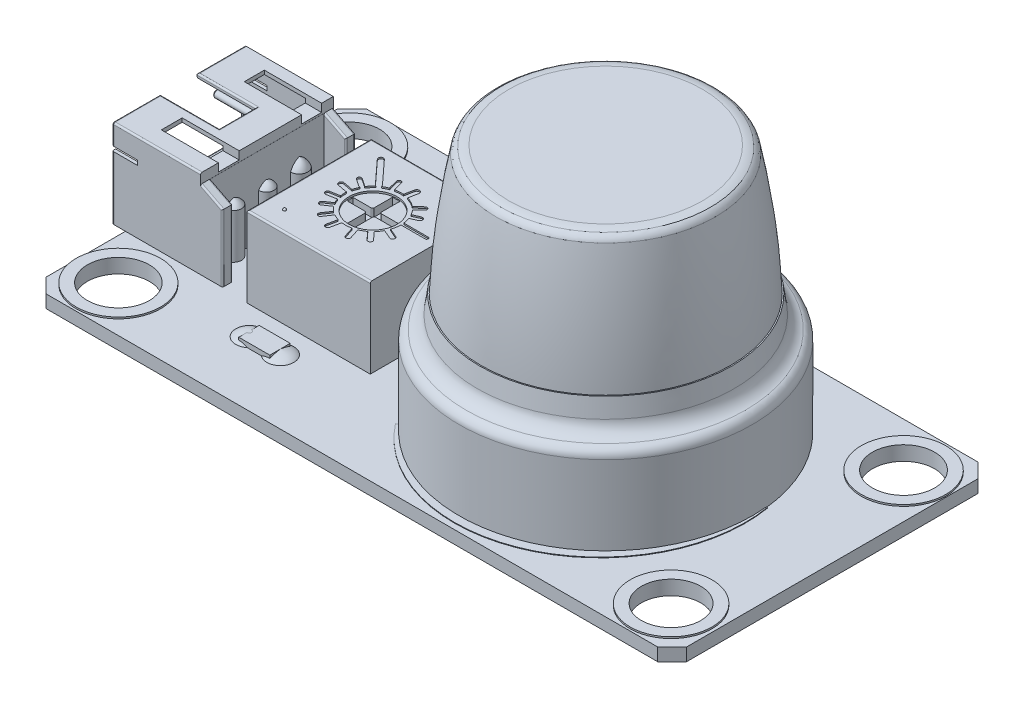
SolidWorks part; units mm, degrees
ref_plane "Alzado" through (0, 0, 0) normal (0, 0, 1) x (1, 0, 0)
ref_plane "Planta" through (0, 0, 0) normal (0, 1, 0) x (1, 0, 0)
ref_plane "Vista lateral" through (0, 0, 0) normal (1, 0, 0) x (0, 0, -1)
sketch "Croquis1" plane through (0, 0, 0) normal (0, 1, 0) x (1, 0, 0)
  line L1 (20, -10) -> (-20, -10)
  line L2 (20, -10) -> (20, 10)
  line L3 (20, 10) -> (-20, 10)
  line L4 (-20, -10) -> (-20, 10)
  line L5 (20, -10) -> (-20, 10) construction
  line L6 (20, 10) -> (-20, -10) construction
  point P0 (0, 0)
  dimension "D1" = 20
  dimension "D2" = 40
extrude "Saliente-Extruir1" add sketch "Croquis1" along normal blind 0.8
chamfer "Chaflán1" distance 0.9 angle 45 4 edges at (20, 0.4, 10) (20, 0.4, -10) (-20, 0.4, -10) (-20, 0.4, 10)
sketch "Croquis2" plane through (0, 0.8, 0) normal (0, 1, 0) x (1, 0, 0)
  circle A0 centre (-17.4865, 7.3544) radius 2.5635
  circle A1 centre (-17.4865, 7.3544) radius 1.8635
  dimension "D1" = 0.7
extrude "Saliente-Extruir2" add sketch "Croquis2" along normal blind 0.1
sketch "Croquis3" plane through (0, 0.8, 0) normal (0, 1, 0) x (1, 0, 0)
  circle A0 centre (-17.3437, -7.2372) radius 2.6343
  circle A2 centre (-17.3437, -7.2372) radius 1.9343
  dimension "D2" = 0.7
extrude "Saliente-Extruir3" add sketch "Croquis3" along normal blind 0.1
sketch "Croquis4" plane through (0, 0.8, 0) normal (0, 1, 0) x (1, 0, 0)
  circle A0 centre (-17.4865, 7.3544) radius 1.8635
extrude "Cortar-Extruir1" cut sketch "Croquis4" against normal through all
sketch "Croquis5" plane through (0, 0.8, 0) normal (0, 1, 0) x (1, 0, 0)
  circle A0 centre (-17.3437, -7.2372) radius 1.9343
extrude "Cortar-Extruir2" cut sketch "Croquis5" against normal through all
sketch "Croquis6" plane through (0, 0.8, 0) normal (0, 1, 0) x (1, 0, 0)
  circle A0 centre (17.306, 7.1429) radius 2.6397
  circle A1 centre (17.306, 7.1429) radius 1.9397
  dimension "D1" = 0.7
extrude "Saliente-Extruir4" add sketch "Croquis6" along normal blind 0.1
sketch "Croquis7" plane through (0, 0.8, 0) normal (0, 1, 0) x (1, 0, 0)
  circle A0 centre (17.306, 7.1429) radius 1.9397
extrude "Cortar-Extruir3" cut sketch "Croquis7" against normal through all
sketch "Croquis8" plane through (0, 0.8, 0) normal (0, 1, 0) x (1, 0, 0)
  circle A0 centre (17.2585, -7.3247) radius 2.5546
  circle A1 centre (17.2585, -7.3247) radius 1.8546
  dimension "D1" = 0.7
extrude "Saliente-Extruir5" add sketch "Croquis8" along normal blind 0.1
sketch "Croquis9" plane through (0, 0.8, 0) normal (0, 1, 0) x (1, 0, 0)
  circle A0 centre (17.2585, -7.3247) radius 1.8546
extrude "Cortar-Extruir4" cut sketch "Croquis9" against normal through all
sketch "Croquis10" plane through (0, 0.8, 0) normal (0, 1, 0) x (1, 0, 0)
  circle A0 centre (5.8533, 0) radius 9.1478
extrude "Saliente-Extruir6" add sketch "Croquis10" along normal blind 5.5
sketch "Croquis12" plane through (0, 0.8, 0) normal (0, 1, 0) x (1, 0, 0)
  line L1 (-4.6304, -4.2212) -> (-12.3417, -4.2212)
  line L2 (-4.6304, -4.2212) -> (-4.6304, 3.5532)
  line L3 (-4.6304, 3.5532) -> (-12.3417, 3.5532)
  line L4 (-12.3417, -4.2212) -> (-12.3417, 3.5532)
  line L5 (-4.6304, -4.2212) -> (-12.3417, 3.5532) construction
  line L6 (-4.6304, 3.5532) -> (-12.3417, -4.2212) construction
  point P0 (-8.486, -0.334)
extrude "Saliente-Extruir7" add sketch "Croquis12" along normal blind 5
sketch "Croquis13" plane through (-12.3417, 0, 0) normal (-1, 0, 0) x (0, 0, 1)
  line L0 (-3.2482, 0.8) -> (-3.2482, 5.4444)
  line L1 (-3.5532, 0.8) -> (4.2212, 0.8) construction
  line L2 (-3.2482, 5.4444) -> (-2.7609, 5.4444)
  line L3 (-2.7609, 5.4444) -> (-2.7609, 0.8)
  line L4 (-3.2482, 0.8) -> (-2.7609, 0.8)
  line L5 (-0.2703, 0.8) -> (-0.2703, 5.4444)
  line L6 (-0.2703, 5.4444) -> (0.334, 5.4444)
  line L7 (0.334, 5.4444) -> (0.334, 0.8)
  line L8 (0.334, 0.8) -> (-0.2703, 0.8)
  line L9 (3.8446, 0.8) -> (3.8446, 5.4444)
  line L10 (3.8446, 5.4444) -> (3.213, 5.4444)
  line L11 (3.213, 5.4444) -> (3.213, 0.8)
  line L12 (3.213, 0.8) -> (3.8446, 0.8)
extrude "Cortar-Extruir6" cut sketch "Croquis13" against normal blind 0.5
sketch "Croquis14" plane through (-12.3417, 0, 0) normal (-1, 0, 0) x (0, 0, 1)
  line L0 (0.5209, 0.8) -> (0.5209, 5.4292)
  line L1 (0.334, 0.8) -> (3.213, 0.8) construction
  line L2 (0.5209, 5.4292) -> (0.6837, 5.4292)
  line L3 (0.6837, 5.4292) -> (0.6837, 0.8)
  line L4 (0.6837, 0.8) -> (0.5209, 0.8)
extrude "Cortar-Extruir7" cut sketch "Croquis14" against normal blind 0.5
sketch "Croquis15" plane through (0, 5.8, 0) normal (0, 1, 0) x (1, 0, 0)
  circle A0 centre (-8.486, -0.1934) radius 1.5
  dimension "D1" = 3
extrude "Cortar-Extruir8" cut sketch "Croquis15" against normal blind 0.2
sketch "Croquis16" plane through (0, 5.6, 0) normal (0, 1, 0) x (1, 0, 0)
  line L1 (-8.6131, -1.6051) -> (-8.2995, -1.6051)
  line L3 (-8.2995, 1.2424) -> (-8.6131, 1.2424)
  line L5 (-7.0615, -0.0779) -> (-7.0615, -0.3129)
  line L7 (-9.9142, -0.3129) -> (-9.9142, -0.0779)
  line L12 (-9.9142, -0.0779) -> (-9.9142, 0)
  line L13 (-9.9142, 0) -> (-8.7038, 0)
  line L14 (-8.7038, 0) -> (-8.7038, 1.2424)
  line L15 (-8.6131, 1.2424) -> (-8.7038, 1.2424)
  line L16 (-8.2995, 1.2424) -> (-8.248, 1.2424)
  line L17 (-8.248, 1.2424) -> (-8.248, 0)
  line L18 (-8.248, 0) -> (-7.0615, 0)
  line L19 (-7.0615, 0) -> (-7.0615, -0.0779)
  line L20 (-8.7038, -0.3729) -> (-8.7038, -1.6051)
  line L21 (-8.7038, -1.6051) -> (-8.6131, -1.6051)
  line L22 (-8.2995, -1.6051) -> (-8.248, -1.6051)
  line L23 (-8.248, -1.6051) -> (-8.248, -0.3729)
  line L24 (-9.9142, -0.3129) -> (-9.9142, -0.3729)
  line L25 (-9.9142, -0.3729) -> (-8.7038, -0.3729)
  line L26 (-7.0615, -0.3129) -> (-7.0615, -0.3729)
  line L27 (-7.0615, -0.3729) -> (-8.248, -0.3729)
extrude "Cortar-Extruir9" cut sketch "Croquis16" against normal blind 0.5
sketch "Croquis17" plane through (0, 5.8, 0) normal (0, 1, 0) x (1, 0, 0)
  line L0 (-6.7524, 0) -> (-5.2555, 0)
  line L2 (-5.249, -0.1934) -> (-6.7416, -0.1934)
  line L3 (-6.8257, -0.7476) -> (-6.2758, -0.9833)
  line L4 (-6.9397, -1.0137) -> (-6.3898, -1.2494)
  line L5 (-8.707, -1.9297) -> (-8.8384, -2.5488)
  line L6 (-8.989, -1.8699) -> (-9.1203, -2.489)
  line L8 (-9.3492, -1.7159) -> (-9.6944, -2.2236)
  line L9 (-7.2099, -1.3914) -> (-6.7759, -1.8719)
  line L10 (-7.4236, -1.5844) -> (-6.9895, -2.0649)
  line L11 (-9.5844, -1.5561) -> (-9.9295, -2.0638)
  line L12 (-7.819, -1.8113) -> (-7.6193, -2.4331)
  line L13 (-8.0863, -1.8972) -> (-7.8866, -2.5189)
  line L15 (-9.8499, -1.2901) -> (-10.3142, -1.6052)
  line L16 (-10.0091, -1.0555) -> (-10.4734, -1.3706)
  line L18 (-6.9446, 0.6958) -> (-6.5446, 0.8736)
  line L19 (-6.8207, 0.4171) -> (-6.4207, 0.5949)
  line L21 (-7.3525, 1.1956) -> (-6.9697, 1.5416)
  line L22 (-7.1786, 1.0031) -> (-6.7957, 1.3491)
  line L24 (-10.1981, -0.7928) -> (-10.742, -0.8882)
  line L25 (-10.2482, -0.507) -> (-10.7921, -0.6024)
  line L27 (-10.2774, -0.1035) -> (-10.8548, 0.0057)
  line L28 (-10.2191, 0.2045) -> (-10.7965, 0.3137)
  line L30 (-10.1497, 0.5884) -> (-10.6088, 0.8957)
  line L31 (-10.0059, 0.8032) -> (-10.465, 1.1105)
  line L33 (-9.6996, 1.1667) -> (-11.036, 2.6242)
  line L34 (-9.4691, 1.378) -> (-10.8056, 2.8355)
  line L36 (-9.1158, 1.5096) -> (-9.2471, 2.0302)
  line L37 (-8.8621, 1.5736) -> (-8.9935, 2.0942)
  line L39 (-8.3111, 1.5825) -> (-8.2061, 2.1257)
  line L40 (-7.9859, 1.5196) -> (-7.8808, 2.0628)
  arc A0 (-6.7524, 0) -> (-6.8485, 0.4078) centre (-8.486, -0.1934) ccw
  arc A1 (-5.249, -0.1934) -> (-5.2555, 0) centre (-5.2319, -0.096) ccw
  circle A2 centre (-8.486, -0.1934) radius 1.5
  arc A3 (-6.8257, -0.7476) -> (-6.8312, -0.7453) centre (-6.8827, -0.8806) ccw
  arc A4 (-6.3898, -1.2494) -> (-6.2758, -0.9833) centre (-6.3328, -1.1163) ccw
  arc A5 (-7.8208, -1.806) -> (-7.4274, -1.5799) centre (-8.486, -0.1934) ccw
  arc A6 (-7.214, -1.3871) -> (-6.9452, -1.0112) centre (-8.486, -0.1934) ccw
  arc A7 (-7.2099, -1.3914) -> (-7.214, -1.3871) centre (-7.3167, -1.4879) ccw
  arc A8 (-6.9895, -2.0649) -> (-6.7759, -1.8719) centre (-6.8827, -1.9684) ccw
  arc A9 (-7.819, -1.8113) -> (-7.8208, -1.806) centre (-7.9527, -1.8542) ccw
  arc A10 (-7.8866, -2.5189) -> (-7.6193, -2.4331) centre (-7.753, -2.476) ccw
  arc A11 (-8.0879, -1.8918) -> (-8.0863, -1.8972) centre (-7.9527, -1.8542) ccw
  arc A12 (-7.4274, -1.5799) -> (-7.4236, -1.5844) centre (-7.3167, -1.4879) ccw
  arc A13 (-6.9452, -1.0112) -> (-6.9397, -1.0137) centre (-6.8827, -0.8806) ccw
  arc A14 (-6.8312, -0.7453) -> (-6.7416, -0.1934) centre (-8.486, -0.1934) ccw
  arc A15 (-8.707, -1.9297) -> (-8.7059, -1.9239) centre (-8.848, -1.8998) ccw
  arc A16 (-9.1203, -2.489) -> (-8.8384, -2.5488) centre (-8.9793, -2.5189) ccw
  arc A17 (-9.3492, -1.7159) -> (-9.346, -1.7111) centre (-9.4668, -1.636) ccw
  arc A18 (-9.9295, -2.0638) -> (-9.6944, -2.2236) centre (-9.8119, -2.1437) ccw
  arc A19 (-9.8499, -1.2901) -> (-9.8452, -1.2868) centre (-9.9295, -1.1728) ccw
  arc A20 (-10.4734, -1.3706) -> (-10.3142, -1.6052) centre (-10.3938, -1.4879) ccw
  arc A21 (-6.9446, 0.6958) -> (-6.9748, 0.678) centre (-6.8827, 0.5564) ccw
  arc A22 (-6.4207, 0.5949) -> (-6.5446, 0.8736) centre (-6.4826, 0.7343) ccw
  arc A23 (-7.3525, 1.1956) -> (-7.3817, 1.157) centre (-7.2655, 1.0994) ccw
  arc A24 (-6.7957, 1.3491) -> (-6.9697, 1.5416) centre (-6.8827, 1.4454) ccw
  arc A25 (-10.1981, -0.7928) -> (-10.1343, -0.7646) centre (-10.2232, -0.6499) ccw
  arc A26 (-10.7921, -0.6024) -> (-10.742, -0.8882) centre (-10.7671, -0.7453) ccw
  arc A27 (-10.2774, -0.1035) -> (-10.2282, -0.105) centre (-10.2482, 0.0505) ccw
  arc A28 (-10.7965, 0.3137) -> (-10.8548, 0.0057) centre (-10.8256, 0.1597) ccw
  arc A29 (-10.1497, 0.5884) -> (-10.0553, 0.5686) centre (-10.0778, 0.6958) ccw
  arc A30 (-10.465, 1.1105) -> (-10.6088, 0.8957) centre (-10.5369, 1.0031) ccw
  arc A31 (-9.6996, 1.1667) -> (-9.6306, 1.123) centre (-9.5844, 1.2724) ccw
  arc A32 (-10.8056, 2.8355) -> (-11.036, 2.6242) centre (-10.9208, 2.7299) ccw
  arc A33 (-9.1158, 1.5096) -> (-9.0794, 1.4471) centre (-8.989, 1.5416) ccw
  arc A34 (-8.9935, 2.0942) -> (-9.2471, 2.0302) centre (-9.1203, 2.0622) ccw
  arc A35 (-8.3111, 1.5825) -> (-8.3139, 1.5425) centre (-8.1485, 1.5511) ccw
  arc A36 (-7.8808, 2.0628) -> (-8.2061, 2.1257) centre (-8.0435, 2.0942) ccw
  arc A37 (-6.8485, 0.4078) -> (-6.8207, 0.4171) centre (-6.8827, 0.5564) ccw
  arc A38 (-6.9748, 0.678) -> (-7.2013, 0.9867) centre (-8.486, -0.1934) ccw
  arc A39 (-7.2013, 0.9867) -> (-7.1786, 1.0031) centre (-7.2655, 1.0994) ccw
  arc A40 (-7.3817, 1.157) -> (-7.9982, 1.4815) centre (-8.486, -0.1934) ccw
  arc A41 (-7.9982, 1.4815) -> (-7.9859, 1.5196) centre (-8.1485, 1.5511) ccw
  arc A42 (-8.3139, 1.5425) -> (-8.862, 1.5101) centre (-8.486, -0.1934) ccw
  arc A43 (-8.862, 1.5101) -> (-8.8621, 1.5736) centre (-8.989, 1.5416) ccw
  arc A44 (-9.0794, 1.4471) -> (-9.4281, 1.2748) centre (-8.486, -0.1934) ccw
  arc A45 (-9.4281, 1.2748) -> (-9.4691, 1.378) centre (-9.5844, 1.2724) ccw
  arc A46 (-9.6306, 1.123) -> (-9.9576, 0.7434) centre (-8.486, -0.1934) ccw
  arc A47 (-9.9576, 0.7434) -> (-10.0059, 0.8032) centre (-10.0778, 0.6958) ccw
  arc A48 (-10.0553, 0.5686) -> (-10.1868, 0.1947) centre (-8.486, -0.1934) ccw
  arc A49 (-10.1868, 0.1947) -> (-10.2191, 0.2045) centre (-10.2482, 0.0505) ccw
  arc A50 (-10.2282, -0.105) -> (-10.2021, -0.5064) centre (-8.486, -0.1934) ccw
  arc A51 (-10.2021, -0.5064) -> (-10.2482, -0.507) centre (-10.2232, -0.6499) ccw
  arc A52 (-10.1343, -0.7646) -> (-10.0043, -1.0524) centre (-8.486, -0.1934) ccw
  arc A53 (-10.0043, -1.0524) -> (-10.0091, -1.0555) centre (-9.9295, -1.1728) ccw
  arc A54 (-9.8452, -1.2868) -> (-9.581, -1.5513) centre (-8.486, -0.1934) ccw
  arc A55 (-9.581, -1.5513) -> (-9.5844, -1.5561) centre (-9.4668, -1.636) ccw
  arc A56 (-9.346, -1.7111) -> (-8.9876, -1.8641) centre (-8.486, -0.1934) ccw
  arc A57 (-8.9876, -1.8641) -> (-8.989, -1.8699) centre (-8.848, -1.8998) ccw
  arc A58 (-8.7059, -1.9239) -> (-8.0879, -1.8918) centre (-8.486, -0.1934) ccw
  point P11 (-6.6078, -0.9985)
  point P18 (2.9909, -1.5468)
  point P19 (-8.9137, -2.2094)
  point P25 (-7.0997, -1.7281)
  point P32 (-7.8528, -2.1651)
  point P46 (-9.6394, -1.8898)
  point P53 (-10.1617, -1.3304)
  point P60 (-6.6827, 0.6453)
  point P67 (-7.0741, 1.2724)
  point P74 (-10.4951, -0.6976)
  point P81 (-10.5369, 0.1051)
  point P88 (-10.3074, 0.8495)
  point P95 (-10.2526, 2.0011)
  point P102 (-9.0546, 1.8019)
  point P109 (-8.096, 1.8226)
extrude "Cortar-Extruir10" cut sketch "Croquis17" against normal blind 0.09
fillet "Redondeo3" radius 0.1 3 edges at (-8.486, 5.8, -3.5532) (-12.3417, 5.8, 0.334) (-8.486, 5.8, 4.2212)
fillet "Redondeo4" radius 0.1 4 edges at (-8.7038, 5.35, 0.3729) (-8.248, 5.35, 0.3729) (-8.7038, 5.35, 0) (-8.248, 5.35, 0)
sketch "Croquis18" plane through (0, 5.8, 0) normal (0, 1, 0) x (1, 0, 0)
  line L0 (-11.2871, -3.0045) -> (-11.1022, -3.0045)
  arc A0 (-11.1022, -3.0045) -> (-11.2871, -3.0045) centre (-11.1947, -3.0045) ccw
revolve "Revolución1" add sketch "Croquis18" angle 360 about L0
sketch "Croquis19" plane through (0, 0.8, 0) normal (0, 1, 0) x (1, 0, 0)
  line L1 (-8.4965, -6.6295) -> (-10.4343, -6.6295)
  line L2 (-8.4965, -6.6295) -> (-8.4965, -5.3534)
  line L3 (-8.4965, -5.3534) -> (-10.4343, -5.3534)
  line L4 (-10.4343, -6.6295) -> (-10.4343, -5.3534)
  line L5 (-8.4965, -6.6295) -> (-10.4343, -5.3534) construction
  line L6 (-8.4965, -5.3534) -> (-10.4343, -6.6295) construction
  point P0 (-9.4654, -5.9914)
extrude "Saliente-Extruir8" add sketch "Croquis19" along normal blind 0.3
ref_plane "Plano1" through (0, 0, 5.97) normal (0, 0, 1) x (1, 0, 0)
sketch "Croquis20" plane through (0, 0, 5.97) normal (0, 0, 1) x (1, 0, 0)
  line L0 (-8.4965, 1.1) -> (-8.4965, 0.8)
  line L1 (-8.4965, 0.8) -> (-7.6501, 0.8)
  spline S0 degree 3 poles (-8.4965, 1.1) (-8.2056, 1.0412) (-7.8872, 0.9962) (-7.6501, 0.8) knots 0 0 0 0 1 1 1 1
revolve "Revolución2" add sketch "Croquis20" angle 360 about L0
sketch "Croquis21" plane through (0, 0, 5.97) normal (0, 0, 1) x (1, 0, 0)
  line L0 (-10.4343, 1.1) -> (-10.4343, 0.8)
  line L1 (-10.4343, 1.1) -> (-10.4343, 0.8) construction
  line L2 (-10.4343, 0.8) -> (-11.22, 0.8)
  line L4 (-11.22, 0.8) -> (-11.2803, 0.8)
  spline S0 degree 2 poles (-10.4343, 1.1) (-10.9186, 1.1271) (-11.2803, 0.8) knots 0 0 0 1 1 1
revolve "Revolución3" add sketch "Croquis21" angle 360 about L0
sketch "Croquis22" plane through (0, 0.8, 0) normal (0, 1, 0) x (1, 0, 0)
  line L1 (-13.9306, 4.1401) -> (-21.6418, 4.1401)
  line L2 (-13.9306, 4.1401) -> (-13.9306, -4.1401)
  line L3 (-13.9306, -4.1401) -> (-21.6418, -4.1401)
  line L4 (-21.6418, 4.1401) -> (-21.6418, -4.1401)
  line L5 (-13.9306, 4.1401) -> (-21.6418, -4.1401) construction
  line L6 (-13.9306, -4.1401) -> (-21.6418, 4.1401) construction
  point P0 (-17.7862, 0)
extrude "Saliente-Extruir9" add sketch "Croquis22" along normal blind 5.5
sketch "Croquis23" plane through (0, 6.3, 0) normal (0, 1, 0) x (1, 0, 0)
  line L0 (-13.9306, 3.5583) -> (-15.2997, 3.5583)
  line L1 (-13.9306, -4.1401) -> (-13.9306, 4.1401) construction
  line L3 (-13.9306, 3.5583) -> (-13.9306, -3.5217)
  line L4 (-13.9306, -4.1401) -> (-13.9306, 4.1401) construction
  line L5 (-13.9306, -3.5217) -> (-15.2997, -3.5217)
  line L6 (-15.2997, 3.5583) -> (-15.2997, -3.5217)
extrude "Cortar-Extruir11" cut sketch "Croquis23" against normal blind 5.5
sketch "Croquis24" plane through (0, 0, 4.1401) normal (0, 0, 1) x (1, 0, 0)
  line L0 (-15.3022, 6.3) -> (-15.3022, 5.6849)
  line L1 (-21.6418, 6.3) -> (-13.9306, 6.3) construction
  line L2 (-15.3022, 5.6849) -> (-13.9306, 4.9885)
  line L3 (-13.9306, 6.3) -> (-13.9306, 0.8) construction
  line L4 (-13.9306, 4.9885) -> (-13.9306, 6.3)
  line L5 (-13.9306, 6.3) -> (-15.3022, 6.3)
extrude "Cortar-Extruir12" cut sketch "Croquis24" against normal blind 9.5
sketch "Croquis25" plane through (0, 0, 4.1401) normal (0, 0, 1) x (1, 0, 0)
  line L0 (-20.8209, 6.3) -> (-21.6418, 6.3)
  line L1 (-21.6418, 6.3) -> (-15.3022, 6.3) construction
  line L2 (-21.6418, 6.3) -> (-21.6418, 0.8)
  line L3 (-21.6418, 0.8) -> (-20.8209, 0.8)
  line L4 (-21.6418, 0.8) -> (-20, 0.8) construction
  line L5 (-20.8209, 0.8) -> (-20.8209, 6.3)
extrude "Cortar-Extruir13" cut sketch "Croquis25" against normal blind 9.5
ref_plane "Plano2" through (0, 0, 2.0901) normal (0, 0, 1) x (1, 0, 0)
ref_plane "Plano3" through (0, 0, 0.0401) normal (0, 0, 1) x (1, 0, 0)
ref_plane "Plano4" through (0, 0, -2.0099) normal (0, 0, 1) x (1, 0, 0)
sketch "Croquis27" plane through (0, 0, 2.0901) normal (0, 0, 1) x (1, 0, 0)
  line L0 (-15.3022, 3.95) -> (-15.3022, 0.8)
  line L1 (-19.1, 0.8) -> (19.1, 0.8) construction
  line L2 (-15.3022, 0.8) -> (-14.8012, 0.8)
  line L3 (-14.8012, 0.8) -> (-14.8012, 3.6)
  spline S0 degree 2 poles (-14.8012, 3.6) (-15.0016, 3.849) (-15.3022, 3.95) knots 0 0 0 1 1 1
  dimension "D1" = 2.8
revolve "Revolución4" add sketch "Croquis27" angle 360 about L0
sketch "Croquis28" plane through (0, 0, 0.0401) normal (0, 0, 1) x (1, 0, 0)
  line L0 (-15.3022, 3.8932) -> (-15.3022, 0.8)
  line L1 (-19.1, 0.8) -> (19.1, 0.8) construction
  line L2 (-15.3022, 0.8) -> (-14.825, 0.8)
  line L3 (-14.825, 0.8) -> (-14.825, 3.55)
  spline S0 degree 2 poles (-14.825, 3.55) (-14.9932, 3.8261) (-15.3022, 3.8932) knots 0 0 0 1 1 1
revolve "Revolución5" add sketch "Croquis28" angle 360 about L0
sketch "Croquis29" plane through (0, 0, -2.0099) normal (0, 0, 1) x (1, 0, 0)
  line L0 (-15.3022, 4.1143) -> (-15.3022, 0.8)
  line L1 (-19.1, 0.8) -> (19.1, 0.8) construction
  line L2 (-15.3022, 0.8) -> (-14.7641, 0.8)
  line L3 (-14.7641, 0.8) -> (-14.7641, 3.55)
  spline S0 degree 2 poles (-14.7641, 3.55) (-14.9211, 3.9482) (-15.3022, 4.1143) knots 0 0 0 1 1 1
revolve "Revolución6" add sketch "Croquis29" angle 360 about L0
sketch "Croquis30" plane through (-20.8209, 0, 0) normal (-1, 0, 0) x (0, 0, 1)
  line L0 (-3.5712, 0.8) -> (-3.5712, 1.2659)
  line L1 (-4.1401, 0.8) -> (4.1401, 0.8) construction
  line L2 (-3.5712, 1.2659) -> (3.5217, 1.2659)
  line L3 (3.5217, 1.2659) -> (3.5217, 0.8)
  line L4 (3.5217, 0.8) -> (-3.5712, 0.8)
extrude "Cortar-Extruir14" cut sketch "Croquis30" against normal blind 4.5
sketch "Croquis31" plane through (-20.8209, 0, 0) normal (-1, 0, 0) x (0, 0, 1)
  line L0 (-3.9344, 6.0631) -> (-3.9344, 1.4969)
  line L1 (-3.9344, 1.4969) -> (3.8803, 1.4969)
  line L3 (3.8803, 6.0631) -> (-3.9344, 6.0631)
  line L4 (3.8803, 6.0631) -> (3.9314, 6.0631)
  line L5 (3.9314, 6.0631) -> (3.9314, 1.4969)
  line L6 (3.9314, 1.4969) -> (3.8803, 1.4969)
extrude "Cortar-Extruir15" cut sketch "Croquis31" against normal blind 4.5
sketch "Croquis32" plane through (0, 0, 4.1401) normal (0, 0, 1) x (1, 0, 0)
  line L0 (-20.8209, 4.7386) -> (-19.2416, 4.7386)
  line L1 (-20.8209, 0.8) -> (-20.8209, 6.3) construction
  line L2 (-19.2416, 4.7386) -> (-19.2416, 5.0288)
  line L3 (-19.2416, 5.0288) -> (-20.8209, 5.0288)
  line L4 (-20.8209, 5.0288) -> (-20.8209, 4.7386)
extrude "Cortar-Extruir16" cut sketch "Croquis32" against normal blind 11.5
sketch "Croquis33" plane through (0, 6.3, 0) normal (0, 1, 0) x (1, 0, 0)
  line L1 (-17.1372, -1.1413) -> (-22.0732, -1.1413)
  line L2 (-17.1372, -1.1413) -> (-17.1372, 1.1413)
  line L3 (-17.1372, 1.1413) -> (-22.0732, 1.1413)
  line L4 (-22.0732, -1.1413) -> (-22.0732, 1.1413)
  line L5 (-17.1372, -1.1413) -> (-22.0732, 1.1413) construction
  line L6 (-17.1372, 1.1413) -> (-22.0732, -1.1413) construction
  point P0 (-19.6052, 0)
extrude "Cortar-Extruir17" cut sketch "Croquis33" against normal blind 3.5
sketch "Croquis34" plane through (0, 6.3, 0) normal (0, 1, 0) x (1, 0, 0)
  line L1 (-14.9619, 3.4134) -> (-18.8796, 3.4134)
  line L2 (-14.9619, 3.4134) -> (-14.9619, 2.1629)
  line L3 (-14.9619, 2.1629) -> (-18.8796, 2.1629)
  line L4 (-18.8796, 3.4134) -> (-18.8796, 2.1629)
  line L5 (-14.9619, 3.4134) -> (-18.8796, 2.1629) construction
  line L6 (-14.9619, 2.1629) -> (-18.8796, 3.4134) construction
  point P0 (-16.9207, 2.7882)
  dimension "D1" = 1.2505
extrude "Cortar-Extruir18" cut sketch "Croquis34" against normal blind 0.5
sketch "Croquis35" plane through (0, 6.3, 0) normal (0, 1, 0) x (1, 0, 0)
  line L1 (-13.7253, -1.7333) -> (-18.8618, -1.7333)
  line L2 (-13.7253, -1.7333) -> (-13.7253, -3.0333)
  line L3 (-13.7253, -3.0333) -> (-18.8618, -3.0333)
  line L4 (-18.8618, -1.7333) -> (-18.8618, -3.0333)
  line L5 (-13.7253, -1.7333) -> (-18.8618, -3.0333) construction
  line L6 (-13.7253, -3.0333) -> (-18.8618, -1.7333) construction
  point P0 (-16.2936, -2.3833)
  dimension "D1" = 1.3
extrude "Cortar-Extruir19" cut sketch "Croquis35" against normal blind 0.5
fillet "Redondeo5" radius 0.1 14 edges at (-20.8209, 5.6644, -4.1401) (-20.8209, 2.7693, -4.1401) (-20.8209, 5.6644, 4.1401) (-20.8209, 2.7693, 4.1401) (-18.0616, 6.3, 4.1401) (-18.979, 6.3, 1.1413) (-17.1372, 6.3, 0) (-18.979, 6.3, -1.1413) (-20.8209, 6.0631, -2.5379) (-20.8209, 6.0631, 2.5364) (-20.8209, 6.3, 2.6407) (-20.8209, 6.3, -2.6407) (-20.8209, 1.2659, -0.0247) (-20.8209, 1.4969, -0.0015)
fillet "Redondeo6" radius 0.1 8 edges at (-13.9306, 2.8943, -3.5583) (-14.6151, 5.3361, -3.5583) (-14.6164, 5.3367, -4.1401) (-13.9306, 2.8943, -4.1401) (-13.9306, 2.8943, 3.5217) (-14.6151, 5.3361, 3.5217) (-13.9306, 2.8943, 4.1401) (-14.6164, 5.3367, 4.1401)
sketch "Croquis36" plane through (-16.3209, 0, 0) normal (-1, 0, 0) x (0, 0, 1)
  circle A0 centre (0, 4.6367) radius 0.2129
  circle A1 centre (-2.3317, 4.6367) radius 0.2129
  circle A2 centre (2.4319, 4.6367) radius 0.2129
extrude "Saliente-Extruir10" add sketch "Croquis36" along normal blind 4.5
fillet "Redondeo7" radius 0.1 3 edges at (-20.8209, 4.6367, 2.6448) (-20.8209, 4.6367, 0.2129) (-20.8209, 4.6367, -2.1188)
sketch "Croquis37" plane through (0, 0.8, 0) normal (0, 1, 0) x (1, 0, 0)
  line L0 (-1.1298, -6.1468) -> (15.0169, 0.9472)
  arc A0 (-1.1298, -6.1468) -> (15.0169, 0.9472) centre (6.0444, -0.5533) ccw
extrude "Saliente-Extruir11" add sketch "Croquis37" along normal blind 0.04
sketch "Croquis38" plane through (0, 6.3, 0) normal (0, 1, 0) x (1, 0, 0)
  circle A2 centre (5.8533, 0) radius 8.1478
  circle A3 centre (5.8533, 0) radius 8.1478
  dimension "D1" = 1
extrude "Saliente-Extruir12" add sketch "Croquis38" along normal blind 2 draft 8
fillet "Redondeo8" radius 1 1 edges at (5.8533, 6.3, 8.1478)
fillet "Redondeo9" radius 0.6 1 edges at (5.8533, 6.3, 9.1478)
sketch "Croquis39" plane through (0, 8.3, 0) normal (0, 1, 0) x (1, 0, 0)
  line L0 (-2.0135, 0) -> (13.72, 0)
  circle A0 centre (5.8533, 0) radius 7.8668 construction
ref_plane "Plano5" through (0, 0, 0) normal (0, 0, 1) x (1, 0, 0)
sketch "Croquis40" plane through (0, 0, 0) normal (0, 0, 1) x (1, 0, 0)
  line L0 (5.8533, 8.3) -> (5.8533, 16.3207)
  line L1 (-2.0135, 8.3) -> (13.72, 8.3) construction
  line L2 (5.8533, 8.3) -> (-1.9415, 8.3)
  line L3 (5.8533, 16.3207) -> (-0.1878, 16.3207)
  spline S0 degree 2 poles (-1.9415, 8.3) (-1.7782, 12.1231) (-1.0011, 15.8654) knots 0 0 0 1 1 1
  spline S1 degree 2 poles (-1.0011, 15.8654) (-0.9179, 16.1067) (-0.6859, 16.2224) knots 0 0 0 1 1 1
  spline S2 degree 2 poles (-0.6859, 16.2224) (-0.4457, 16.3123) (-0.1878, 16.3207) knots 0 0 0 1 1 1
revolve "Revolución9" add sketch "Croquis40" angle 360 about L0
